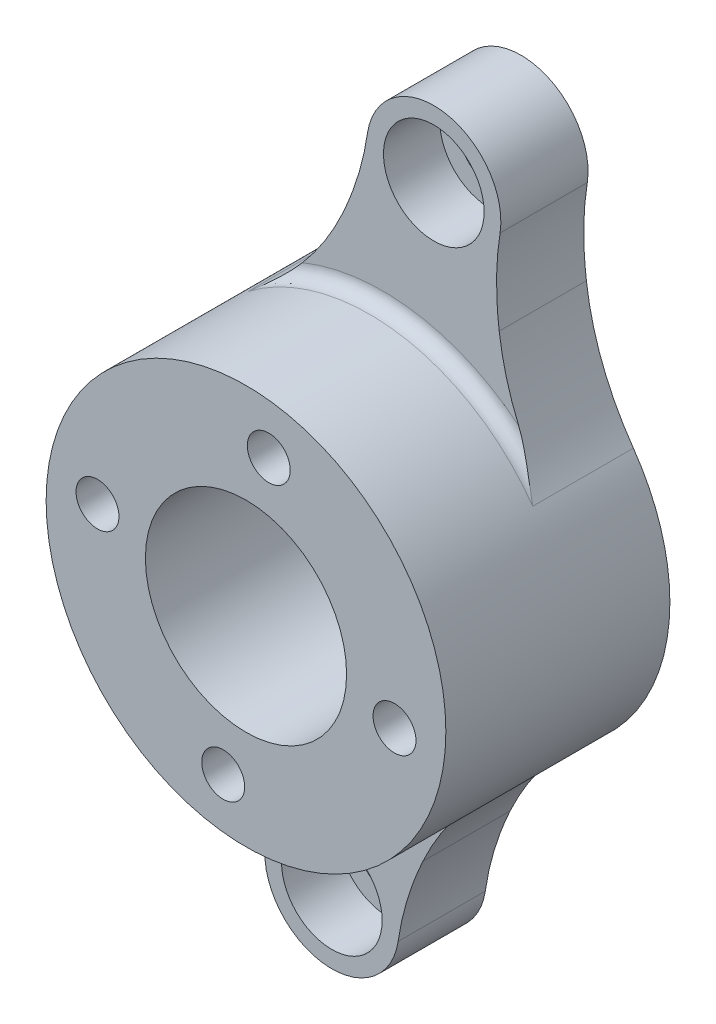
SolidWorks part; units mm, degrees
ref_plane "Front Plane" through (0, 0, 0) normal (0, 0, 1) x (1, 0, 0)
ref_plane "Top Plane" through (0, 0, 0) normal (0, 1, 0) x (1, 0, 0)
ref_plane "Right Plane" through (0, 0, 0) normal (1, 0, 0) x (0, 0, -1)
sketch "Sketch1" plane through (0, 0, 0) normal (0, 0, 1) x (1, 0, 0)
  arc A0 (-11.1727, 5.6055) -> (-12.3393, -1.9981) centre (0, 0) ccw
  circle A4 centre (0, 0) radius 7.5 construction
  circle A8 centre (0, 0) radius 7.5
  arc A11 (8.7426, 24.0121) -> (-1.1417, 25.5287) centre (3.8005, 24.7704) ccw
  circle A12 centre (0, 0) radius 12.5 construction
  arc A13 (1.1532, -25.4498) -> (-8.7299, -23.9334) centre (-3.8005, -24.7704) cw
  arc A14 (11.1727, -5.6055) -> (12.3393, 1.9981) centre (0, 0) ccw
  circle A15 centre (-3.8005, -24.7704) radius 2.25
  circle A16 centre (3.8005, 24.7704) radius 2.25
  spline S0 degree 3 poles (8.7426, 24.0121) (7.4898, 16.3579) (11.0185, 9.6073) (12.3393, 1.9981) knots 0 0 0 0 1 1 1 1
  spline S1 degree 3 poles (-1.1417, 25.5287) (-2.2413, 17.8509) (-7.6314, 12.4687) (-11.1727, 5.6055) knots 0 0 0 0 1 1 1 1
  spline S2 degree 3 poles (1.1417, -25.5287) (2.2413, -17.8509) (7.6314, -12.4687) (11.1727, -5.6055) knots 0 0 0 0 1 1 1 1
  spline S3 degree 3 poles (-8.7426, -24.0121) (-7.4898, -16.3579) (-11.0185, -9.6073) (-12.3393, -1.9981) knots 0 0 0 0 1 1 1 1
  point P10 (3.8005, 24.7704)
  point P25 (0, 0)
  dimension "D1" = 5
extrude "Boss-Extrude1" add sketch "Sketch1" along normal blind 6.5 contours S3 A13 S2 A14 S0 A11 S1 A0 A16 A15 A8 region at (-4.743, 14.839, 0)
sketch "Sketch2" plane through (0, 0, 6.5) normal (0, 0, 1) x (1, 0, 0)
  circle A0 centre (3.8005, 24.7704) radius 3.75
  circle A1 centre (-3.8005, -24.7704) radius 3.75
extrude "Cut-Extrude1" cut sketch "Sketch2" against normal blind 4.2
sketch "Sketch3" plane through (0, 0, 6.5) normal (0, 0, 1) x (1, 0, 0)
  circle A2 centre (0, 0) radius 7.5 construction
  circle A3 centre (0, 0) radius 7.5
  circle A4 centre (0, 0) radius 14.9
extrude "Boss-Extrude2" add sketch "Sketch3" along normal blind 10.2 and the other way up to surface (6.5 mm away) other way up to face at (0, 0, 0)
sketch "Sketch4" plane through (0, 0, 16.7) normal (0, 0, 1) x (1, 0, 0)
  circle A4 centre (-1.6985, -11.0705) radius 1.6
  circle A5 centre (-11.0705, 1.6985) radius 1.6
  circle A6 centre (1.6985, 11.0705) radius 1.6
  circle A7 centre (11.0705, -1.6985) radius 1.6
  point P19 (0, 0)
  dimension "D1" = 4
extrude "Cut-Extrude2" cut sketch "Sketch4" against normal through all
sketch "Sketch6" plane through (0, 0, 0) normal (0, 0, -1) x (-1, 0, 0)
  line L0 (-11.0705, 1.5346) -> (-13.8705, -0.0819)
  line L1 (-1.5346, -11.0705) -> (0.0819, -13.8705)
  line L2 (0.0819, -13.8705) -> (3.3151, -13.8705)
  line L3 (3.3151, -13.8705) -> (4.9317, -11.0705)
  line L4 (4.9317, -11.0705) -> (3.3151, -8.2705)
  line L5 (3.3151, -8.2705) -> (0.0819, -8.2705)
  line L6 (0.0819, -8.2705) -> (-1.5346, -11.0705)
  line L7 (-13.8705, -0.0819) -> (-13.8705, -3.3151)
  line L8 (-13.8705, -3.3151) -> (-11.0705, -4.9317)
  line L9 (-11.0705, -4.9317) -> (-8.2705, -3.3151)
  line L10 (-8.2705, -3.3151) -> (-8.2705, -0.0819)
  line L11 (-8.2705, -0.0819) -> (-11.0705, 1.5346)
  line L12 (1.5346, 11.0705) -> (-0.0819, 13.8705)
  line L13 (-0.0819, 13.8705) -> (-3.3151, 13.8705)
  line L14 (-3.3151, 13.8705) -> (-4.9317, 11.0705)
  line L15 (-4.9317, 11.0705) -> (-3.3151, 8.2705)
  line L16 (-3.3151, 8.2705) -> (-0.0819, 8.2705)
  line L17 (-0.0819, 8.2705) -> (1.5346, 11.0705)
  line L18 (11.0705, -1.5346) -> (13.8705, 0.0819)
  line L19 (13.8705, 0.0819) -> (13.8705, 3.3151)
  line L20 (13.8705, 3.3151) -> (11.0705, 4.9317)
  line L21 (11.0705, 4.9317) -> (8.2705, 3.3151)
  line L22 (8.2705, 3.3151) -> (8.2705, 0.0819)
  line L23 (8.2705, 0.0819) -> (11.0705, -1.5346)
  circle A0 centre (1.6985, -11.0705) radius 2.8 construction
  point P30 (0, 0)
  dimension "D1" = 4
extrude "Cut-Extrude3" cut sketch "Sketch6" against normal blind 10
fillet "Fillet2" radius 1 2 edges at (-2.2596, -14.7277, 6.5) (2.2596, 14.7277, 6.5)
fillet "Fillet4" radius 20 4 edges at (-6.3642, 13.4724, 3.75) (10.1105, 10.9448, 3.75) (6.3642, -13.4724, 3.75) (-10.1105, -10.9448, 3.75)
